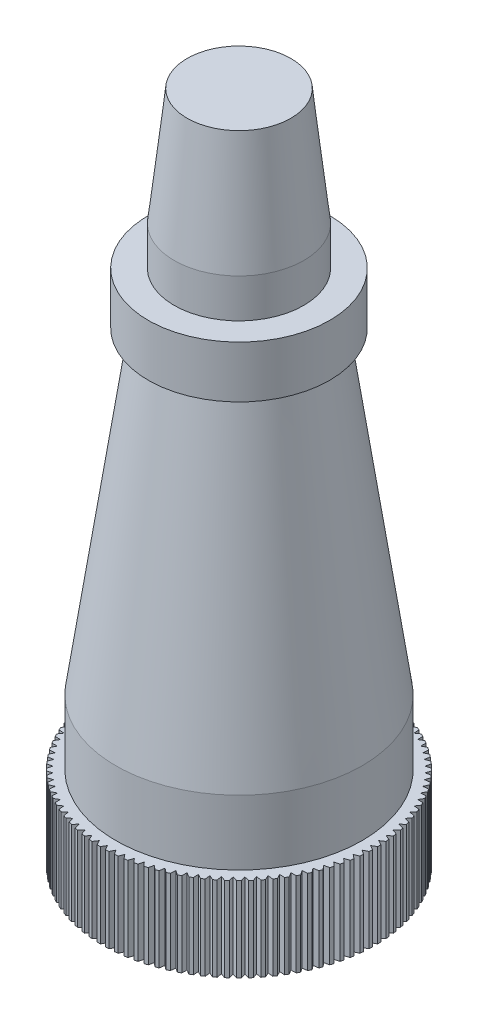
SolidWorks part; units mm, degrees
material "Zinc AC41A Alloy, As Cast"
ref_plane "Front Plane" through (0, 0, 0) normal (0, 0, 1) x (1, 0, 0)
ref_plane "Top Plane" through (0, 0, 0) normal (0, 1, 0) x (1, 0, 0)
ref_plane "Right Plane" through (0, 0, 0) normal (1, 0, 0) x (0, 0, -1)
sketch "Sketch1" plane through (0, 0, 0) normal (0, 0, 1) x (1, 0, 0)
  line L0 (0, 2) -> (0, 42)
  line L1 (0, 42) -> (7, 42)
  line L2 (7, 42) -> (7, 38)
  line L3 (7, 38) -> (0, 38)
  line L4 (6, 38) -> (9.5, 13.5)
  line L5 (9.5, 13.5) -> (9.5, 8.5)
  line L6 (0, 2) -> (10.5, 2)
  line L7 (10.5, 2) -> (10.5, 8.5)
  line L8 (10.5, 8.5) -> (0, 8.5)
  line L9 (0, 2) -> (0, 0)
  line L10 (0, 0) -> (7, 0)
  line L11 (7, 0) -> (7, 2)
  line L12 (5, 42) -> (5, 45)
  line L13 (5, 45) -> (4, 54)
  line L14 (4, 54) -> (0, 54)
  line L15 (0, 54) -> (0, 42)
  dimension "D1" = 7
  dimension "D2" = 10.5
  dimension "D3" = 1
  dimension "D4" = 6.5
  dimension "D5" = 5
  dimension "D6" = 4
  dimension "D7" = 7
  dimension "D8" = 1
  dimension "D9" = 2
  dimension "D10" = 42
  dimension "D11" = 5
  dimension "D12" = 12
  dimension "D13" = 3
  dimension "D14" = 4
revolve "Revolve1" add sketch "Sketch1" angle 360 about L0 region at (5.25, 5.25, 0) region at (3.5, 1, 0) region at (4.1028, 22.0609, 0) region at (3.5, 40, 0) region at (2.3243, 47.7568, 0)
sketch "Sketch3" plane through (0, 0, 0) normal (0, -1, 0) x (1, 0, 0)
  circle A0 centre (0, 0) radius 7 construction
  circle A1 centre (0, 0) radius 7
  circle A2 centre (0, 0) radius 8.5
  circle M3 centre (0, 0) radius 7
  dimension "D1" = 1.5
extrude "Cut-Extrude1" cut sketch "Sketch3" against normal blind 10 contours A2 M3 region at (-8.2596, 0, 0)
ref_axis "Axis1" through (0, 8.5, 0) along (0, -1, 0)
sketch "Sketch4" plane through (0, 2, 0) normal (0, -1, 0) x (1, 0, 0)
  line L0 (0, 10.7995) -> (0, 10.15) construction
  line L1 (0, 10.15) -> (0.375, 10.7995)
  line L2 (0.375, 10.7995) -> (-0.375, 10.7995)
  line L3 (0, 10.15) -> (-0.375, 10.7995)
  circle A0 centre (0, 0) radius 10.5 construction
  point P5 (0, 10.5)
  point P6 (0, 0)
  dimension "D1" = 0.35
  dimension "D2" = 60
  dimension "D3" = 0.75
extrude "Cut-Extrude2" cut sketch "Sketch4" against normal up to surface (6.5 mm away) up to face at (9.5, 8.5, 0)
pattern_circular "CirPattern1" count 100 over 360 about axis through (0, 8.5, 0) along (0, -1, 0) of "Cut-Extrude2"
